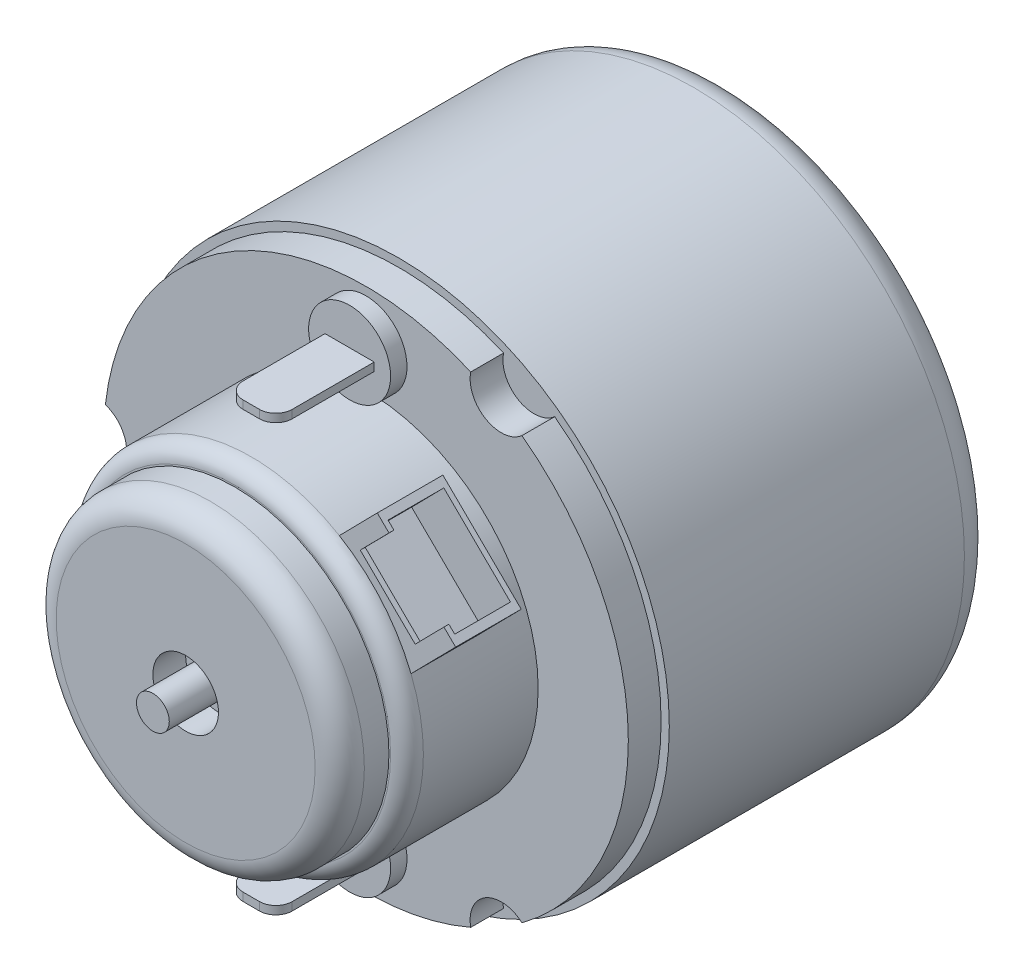
SolidWorks part; units mm, degrees
note: '?' marks a value the reader was unsure of.
ref_plane "Plano frontal" through (0, 0, 0) normal (0, 0, 1) x (1, 0, 0)
ref_plane "Plano superior" through (0, 0, 0) normal (0, 1, 0) x (1, 0, 0)
ref_plane "Plano direito" through (0, 0, 0) normal (1, 0, 0) x (0, 0, -1)
sketch "Esboço1" plane through (0, 0, 0) normal (0, 0, 1) x (1, 0, 0)
  circle A0 centre (0, 0) radius 16.5
  dimension "D1" = 33
extrude "Ressalto-extrusão1" add sketch "Esboço1" along normal blind 20
sketch "Esboço4" plane through (0, 0, 0) normal (0, 0, -1) x (-1, 0, 0)
  line L0 (0, 0) -> (-11.2583, -6.5) construction
  line L1 (0, 0) -> (0, 13) construction
  line L2 (0, 0) -> (11.2583, -6.5) construction
  circle A0 centre (0, 0) radius 3.5
  circle A1 centre (0, 13) radius 1.25
  circle A2 centre (11.2583, -6.5) radius 1.25
  circle A3 centre (-11.2583, -6.5) radius 1.25
  dimension "D1" = 7
  dimension "D2" = 2.5
  dimension "D3" = 2.5
  dimension "D4" = 2.5
  dimension "D5" = 13
  dimension "D6" = 120
  dimension "D7" = 13
  dimension "D8" = 120
  dimension "D9" = 13
extrude "Ressalto-extrusão4" add sketch "Esboço4" along normal blind 1.5 contours A0
sketch "Esboço14" plane through (0, 0, -1.5) normal (0, 0, -1) x (-1, 0, 0)
  circle A0 centre (0, 0) radius 1
  dimension "D1" = 2
extrude "Ressalto-extrusão7" add sketch "Esboço14" along normal blind 4
hole_wizard "Furo roscado de M2.5x0.451" positions "Esboço16" profile "Esboço15" tap size "M2.5x0.45" standard "Métrico Ansi"
sketch "Esboço16" plane through (0, 0, 0) normal (0, 0, -1) x (-1, 0, 0)
  line L0 (0, 13) -> (0, 0) construction
  line L1 (0, 0) -> (11.2583, -6.5) construction
  line L3 (0, 0) -> (-11.2583, -6.5) construction
  line L4 (0, 0) -> (11.2583, 6.5) construction
  line L6 (0, 0) -> (0, -13) construction
  line L8 (0, 0) -> (-11.2583, 6.5) construction
  point P0 (11.2583, -6.5)
  point P1 (0, 13)
  point P3 (-11.2583, -6.5)
  point P31 (11.2583, 6.5)
  point P33 (0, -13)
  point P35 (-11.2583, 6.5)
  dimension "D1" = 13
  dimension "D2" = 13
  dimension "D3" = 13
  dimension "D4" = 120
  dimension "D5" = 120
  dimension "D6" = 13
  dimension "D7" = 13
  dimension "D8" = 13
  dimension "D9" = 120
  dimension "D10" = 120
  dimension "D11" = 60
sketch "Esboço15" plane through (-11.2583, -6.5, 0) normal (1, 0, 0) x (0, 1, 0)
  line L0 (0, 0) -> (0, 4.1159)
  line L1 (0, 4.1159) -> (1.025, 3.5)
  line L2 (1.025, 3.5) -> (1.025, 0)
  line L5 (1.025, 0) -> (0, 0)
  line L10 (0, 4.1159) -> (-1.025, 3.5) construction
  line L11 (0, -6.35) -> (0, 107.95) construction
  dimension "Tap Drill Dia." = 2.05
  dimension "Tap Drill Depth" = 3.5
  dimension "Drill Angle" = 118
ref_axis "Eixo1" through (0, 0, -9.675) along (0, 0, 1)?
fillet "Filete1" radius 2 1 edges at (16.5, 0, 0)
sketch "Esboço17" plane through (0, 0, 20) normal (0, 0, 1) x (1, 0, 0)
  line L0 (0, 0) -> (8.25, 14.2894) construction
  line L1 (0, 0) -> (-16.5, 0) construction
  line L2 (0, 0) -> (8.25, -14.2894) construction
  arc A0 (9.5098, -12.8671) -> (9.5098, 12.8671) centre (0, 0) ccw
  circle A1 centre (0, 0) radius 16.5
  arc A2 (6.5526, -15.1431) -> (9.838, -13.2463) centre (0, 0) ccw
  arc A3 (-16.3906, -1.8968) -> (-16.3906, 1.8968) centre (-16.5, 0) ccw
  arc A4 (9.838, -13.2463) -> (6.5526, -15.1431) centre (8.25, -14.2894) ccw
  arc A5 (6.5526, 15.1431) -> (9.838, 13.2463) centre (8.25, 14.2894) ccw
  arc A6 (9.838, 13.2463) -> (6.5526, 15.1431) centre (0, 0) ccw
  arc A7 (6.3884, 14.6693) -> (6.3884, -14.6693) centre (0, 0) ccw
  arc A8 (-16.3906, 1.8968) -> (-16.3906, -1.8968) centre (0, 0) ccw
  dimension "D4" = 3.8
  dimension "D5" = 3.8
  dimension "D6" = 3.8
  dimension "D7" = 32
  dimension "D2" = 120
  dimension "D3" = 120
  dimension "D1" = 0
extrude "Ressalto-extrusão9" add sketch "Esboço17" along normal blind 2 contours A5 A2 A3 A4
sketch "Esboço18" plane through (0, 0, 22) normal (0, 0, 1) x (1, 0, 0)
  circle A0 centre (0, 0) radius 10.5
  dimension "D1" = 21
extrude "Ressalto-extrusão10" add sketch "Esboço18" along normal blind 8
fillet "Filete2" radius 1 1 edges at (10.5, 0, 30)
sketch "Esboço19" plane through (0, 0, 30) normal (0, 0, 1) x (1, 0, 0)
  circle A0 centre (0, 0) radius 9.4
  dimension "D1" = 18.8
extrude "Ressalto-extrusão11" add sketch "Esboço19" along normal blind 3
fillet "Filete3" radius 1.5 1 edges at (9.4, 0, 33)
sketch "Esboço20" plane through (0, 0, 33) normal (0, 0, 1) x (1, 0, 0)
  circle A0 centre (0, 0) radius 2
  dimension "D1" = 4
extrude "Corte-extrusão1" cut sketch "Esboço20" against normal blind 2
sketch "Esboço21" plane through (0, 0, 31) normal (0, 0, 1) x (1, 0, 0)
  circle A0 centre (0, 0) radius 1
  dimension "D1" = 2
extrude "Ressalto-extrusão13" add sketch "Esboço21" along normal blind 4
sketch "Esboço22" plane through (0, 0, 22) normal (0, 0, 1) x (1, 0, 0)
  line L0 (0, -13) -> (0, 0) construction
  line L1 (0, 0) -> (0, 13) construction
  circle A0 centre (0, 13) radius 2.5
  circle A1 centre (0, -13) radius 2.5
  dimension "D3" = 5
  dimension "D4" = 5
  dimension "D1" = 13
  dimension "D2" = 13
extrude "Ressalto-extrusão15" add sketch "Esboço22" along normal blind 1 separate body
sketch "Esboço23" plane through (0, 0, 23) normal (0, 0, 1) x (1, 0, 0)
  line L1 (1.5, -12.75) -> (-1.5, -12.75)
  line L2 (1.5, -12.75) -> (1.5, -13.25)
  line L3 (1.5, -13.25) -> (-1.5, -13.25)
  line L4 (-1.5, -12.75) -> (-1.5, -13.25)
  line L5 (1.5, -12.75) -> (-1.5, -13.25) construction
  line L6 (1.5, -13.25) -> (-1.5, -12.75) construction
  line L7 (1.5, 13.25) -> (-1.5, 13.25)
  line L8 (1.5, 13.25) -> (1.5, 12.75)
  line L9 (1.5, 12.75) -> (-1.5, 12.75)
  line L10 (-1.5, 13.25) -> (-1.5, 12.75)
  line L11 (1.5, 13.25) -> (-1.5, 12.75) construction
  line L12 (1.5, 12.75) -> (-1.5, 13.25) construction
  point P0 (0, -13)
  point P6 (0, 13)
  dimension "D1" = 3
  dimension "D2" = 3
  dimension "D3" = 0.5
  dimension "D4" = 0.5
extrude "Ressalto-extrusão16" add sketch "Esboço23" along normal blind 6
fillet "Filete4" radius 1 2 edges at (1.5, -13, 29) (-1.5, -13, 29)
fillet "Filete5" radius 1 2 edges at (1.5, 13, 29) (-1.5, 13, 29)
ref_plane "Plano1" through (7.3613, 7.4874, 0) normal (0.7011, 0.7131, 0) x (-0.7131, 0.7011, 0)
sketch "Esboço24" plane through (7.3613, 7.4874, 0) normal (0.7011, 0.7131, 0) x (-0.7131, 0.7011, 0)
  line L0 (10.5, 22) -> (-10.5, 22) construction
  line L1 (2.491, 29) -> (-4.209, 29)
  line L2 (2.491, 29) -> (2.491, 25)
  line L3 (2.491, 25) -> (-4.209, 25)
  line L4 (-4.209, 29) -> (-4.209, 25)
  line L5 (2.491, 29) -> (-4.209, 25) construction
  line L6 (2.491, 25) -> (-4.209, 29) construction
  line L7 (8.2196, 28) -> (8.2196, 23) construction
  point P0 (-0.859, 27)
  dimension "D1" = 6.7
  dimension "D2" = 4
  dimension "D3" = 5
  dimension "D4" = 5.7287
extrude "Ressalto-extrusão17" add sketch "Esboço24" along normal blind 3 and the other way up to next
sketch "Esboço25" plane through (9.4645, 9.6267, 0) normal (0.7011, 0.7131, 0) x (0.7131, -0.7011, 0)
  line L5 (3.709, -28.5) -> (-1.991, -28.5)
  line L6 (3.709, -28.5) -> (3.709, -28.7)
  line L7 (3.709, -28.7) -> (-1.991, -28.7)
  line L8 (3.709, -28.5) -> (3.709, -25.5)
  line L9 (3.709, -25.5) -> (-1.991, -25.5)
  line L10 (-1.991, -25.5) -> (-1.991, -28.5)
  line L11 (-1.991, -28.5) -> (3.709, -28.5)
  line L12 (3.709, -28.5) -> (3.709, -25.5)
  line L13 (3.709, -25.5) -> (-1.991, -25.5)
  line L14 (-1.991, -25.5) -> (-1.991, -28.5)
  line L15 (-1.991, -28.5) -> (3.709, -28.5)
  line L16 (-1.991, -28.5) -> (-1.991, -28.7)
  line L17 (-1.991, -25.5) -> (3.709, -25.5)
  line L18 (-1.991, -25.5) -> (-1.991, -25.3)
  line L19 (-1.991, -25.3) -> (3.709, -25.3)
  line L20 (3.709, -25.5) -> (3.709, -25.3)
  dimension "D2" = 0.2
  dimension "D3" = 0.2
  dimension "D1" = 0.5
extrude "Corte-extrusão2" cut sketch "Esboço25" against normal blind 2.8 contours L13 L14 L5 L12 | L5 L16 L7 L6 | L13 L20 L19 L18
sketch "Esboço26" plane through (9.4645, 9.6267, 0) normal (0.7011, 0.7131, 0) x (0.7131, -0.7011, 0)
  line L0 (-2.491, -29) -> (4.209, -29) construction
  line L1 (-1.491, -29) -> (3.209, -29)
  line L2 (-1.491, -29) -> (-1.491, -28.7)
  line L3 (-1.491, -28.7) -> (3.209, -28.7)
  line L4 (3.209, -29) -> (3.209, -28.7)
  line L5 (3.709, -28.7) -> (-1.991, -28.7) construction
  line L6 (-2.491, -25) -> (-2.491, -29) construction
  line L7 (4.209, -29) -> (4.209, -25) construction
  dimension "D1" = 1
  dimension "D2" = 1
extrude "Corte-extrusão3" cut sketch "Esboço26" against normal blind 2.5
ref_plane "Plano2" through (0, 0, 11) normal (0, 0, -1) x (-1, 0, 0)
